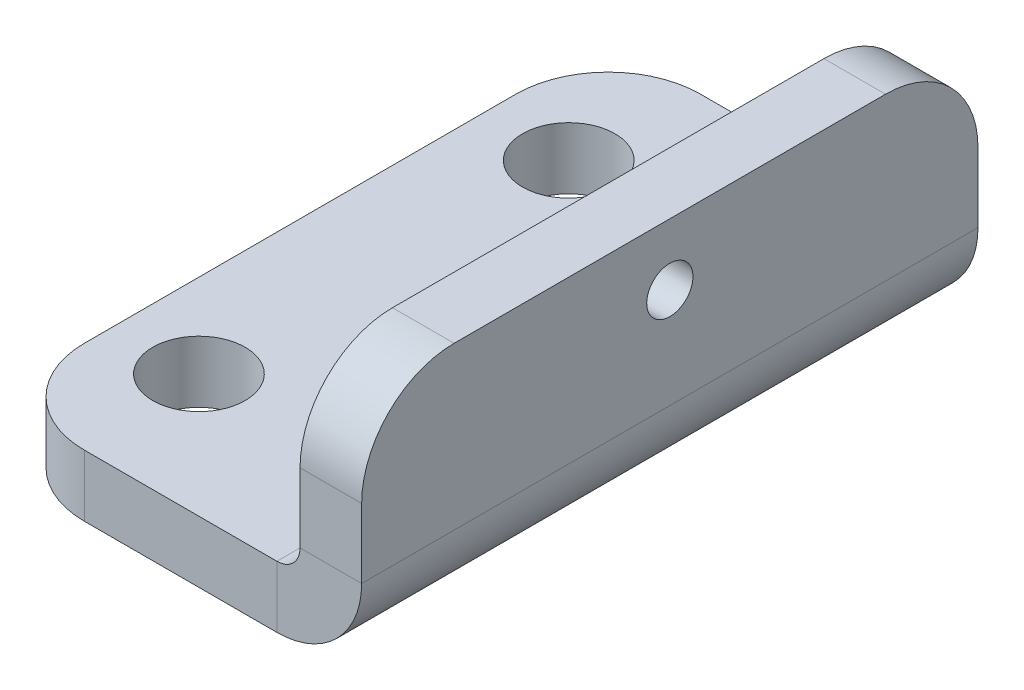
SolidWorks part; units mm, degrees
note: The reader was unsure of these and kept them because the rebuilt part matched: flange length of "Edge-Flange1".
ref_plane "Front Plane" through (0, 0, 0) normal (0, 0, 1) x (1, 0, 0)
ref_plane "Top Plane" through (0, 0, 0) normal (0, 1, 0) x (1, 0, 0)
ref_plane "Right Plane" through (0, 0, 0) normal (1, 0, 0) x (0, 0, -1)
sketch "Sketch1" plane through (0, 0, 0) normal (0, 1, 0) x (1, 0, 0)
  line L0 (0, 7) -> (0, -7)
  line L1 (3, 10) -> (12, 10)
  line L2 (3, -10) -> (12, -10)
  line L3 (12, 10) -> (12, -10)
  arc A0 (0, -7) -> (3, -10) centre (3, -7) ccw
  arc A1 (0, 7) -> (3, 10) centre (3, 7) cw
  circle A2 centre (2.72, 6) radius 1.5
  circle A3 centre (2.72, -6) radius 1.5
  point P0 (0, 6)
  point P4 (0, 0)
  point P8 (0, -6)
  point P11 (0, -10)
  point P14 (0, 10)
  dimension "D6" = 3
  dimension "D7" = 3
  dimension "D8" = 3
  dimension "D1" = 20
  dimension "D2" = 12
  dimension "D3" = 12
  dimension "D4" = 6
  dimension "D5" = 12
  dimension "D9" = 9.28
  dimension "D10" = 9.28
base flange "Base-Flange1" sketch "Sketch1" thickness 2 reverse thickness direction yes parameters "D1"=0.7366
edge flange "Edge-Flange1" sketch "Sketch8" flange angle 90 flange length 8 flange position material inside bend radius 0.75 thickness 2 relief rectangular parameters "D6"=10
sketch "Sketch8" plane through (12, 2, 0) normal (1, 0, 0) x (0, 0, -1)
  line L2 (-10, 0) -> (-10, 6)
  line L3 (-10, 6) -> (10, 6)
  line L4 (10, 6) -> (10, 0)
  line L7 (-10, 0) -> (10, 0) construction
  line L8 (-10, 0) -> (10, 0)
bend "EdgeBend1" bend radius 0.75 bend angle 90 parameters "D5"=1
sketch "Sketch9" plane through (10, 0, 0) normal (-1, 0, 0) x (0, 0, 1)
  line L0 (-10, 8) -> (10, 8) construction
  circle A0 centre (0, 6) radius 0.75
  dimension "D1" = 2
  dimension "D2" = 1.5
extrude "Cut-Extrude1" cut sketch "Sketch9" against normal blind 10 normal cut yes
fillet "Fillet1" radius 3 2 edges at (11, 8, 10) (11, 8, -10)
scale "Scale1" scale about centroid uniform scaling yes scale factor 1.8
sketch "Bend-Lines1" [suppressed] plane through (0, 0, 0) normal (0, 1, 0) x (1, 0, 0)
sketch "Bounding-Box1" [suppressed] plane through (0, 0, 0) normal (0, 1, 0) x (1, 0, 0)
sheet metal parameters "Sheet-Metal1" thickness 2 parameters "D1"=0.7366
flat pattern "Flat-Pattern1" [suppressed]
sketch "Bend-Lines2" plane through (0, 0, 0) normal (0, 1, 0) x (1, 0, 0)
sketch3d "Bounding-Box2" [suppressed]
  line L0 (-3, 17, 0) -> (-3, -3, 0) construction
  line L1 (9, 17, 0) -> (9, -3, 0) construction
  line L2 (-3, 17, 0) -> (9, 17, 0) construction
  line L3 (-3, -3, 0) -> (9, -3, 0) construction
sheet metal parameters "Sheet-Metal2" thickness 2 parameters "D1"=0.7366
flat pattern "Flat-Pattern1"
sketch "Bend-Lines2" plane through (0, 0, 0) normal (0, -1, 0) x (-1, 0, 0)
  line L0 (-10.6244, 10) -> (-10.6244, -10) construction
  line L1 (-10.6244, 10) -> (-10.6244, -10) construction
sketch3d "Bounding-Box2" [suppressed]
  line L0 (3, 17, 0) -> (3, -3, 0) construction
  line L1 (-14.2489, 17, 0) -> (-14.2489, -3, 0) construction
  line L2 (3, 17, 0) -> (-14.2489, 17, 0) construction
  line L3 (3, -3, 0) -> (-14.2489, -3, 0) construction
bend of the flat pattern "Flatten-<EdgeBend1>1"
sheet metal parameters "Sheet-Metal3" thickness 2 parameters "D1"=0.7366
flat pattern "Flat-Pattern1"
sketch "Bend-Lines2" plane through (0, 0, 0) normal (0, -1, 0) x (-1, 0, 0)
  line L0 (-10.6244, 10) -> (-10.6244, -10) construction
  line L1 (-10.6244, 10) -> (-10.6244, -10) construction
sketch3d "Bounding-Box2" [suppressed]
  line L0 (3, 17, 0) -> (3, -3, 0) construction
  line L1 (-14.2489, 17, 0) -> (-14.2489, -3, 0) construction
  line L2 (3, 17, 0) -> (-14.2489, 17, 0) construction
  line L3 (3, -3, 0) -> (-14.2489, -3, 0) construction
bend of the flat pattern "Flatten-<EdgeBend1>1"
sheet metal parameters "Sheet-Metal4" thickness 2 parameters "D1"=0.7366
flat pattern "Flat-Pattern1"
sketch "Bend-Lines2" plane through (0, 0, 0) normal (0, -1, 0) x (-1, 0, 0)
  line L0 (-10.6244, 10) -> (-10.6244, -10) construction
  line L1 (-10.6244, 10) -> (-10.6244, -10) construction
sketch3d "Bounding-Box2" [suppressed]
  line L0 (3, 17, 0) -> (3, -3, 0) construction
  line L1 (-14.2489, 17, 0) -> (-14.2489, -3, 0) construction
  line L2 (3, 17, 0) -> (-14.2489, 17, 0) construction
  line L3 (3, -3, 0) -> (-14.2489, -3, 0) construction
bend of the flat pattern "Flatten-<EdgeBend1>1"
